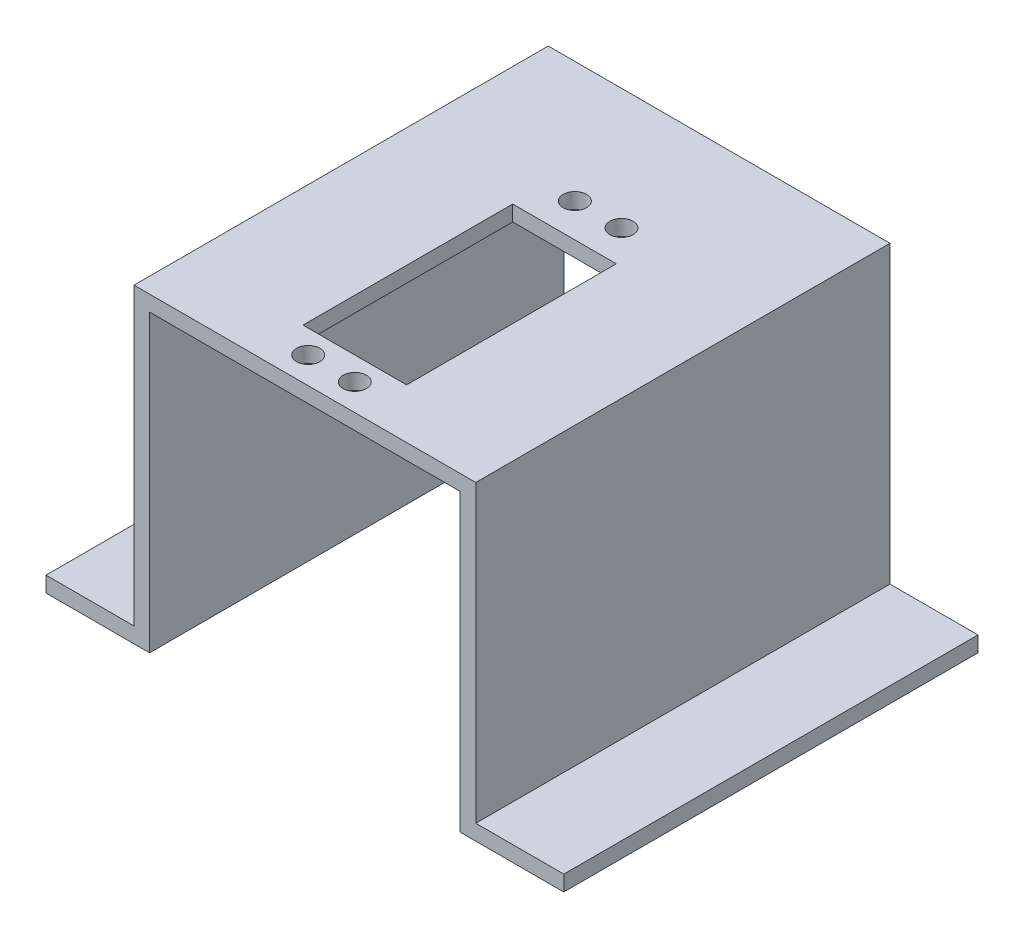
SolidWorks part; units mm, degrees
ref_plane "Front Plane" through (0, 0, 0) normal (0, 0, 1) x (1, 0, 0)
ref_plane "Top Plane" through (0, 0, 0) normal (0, 1, 0) x (1, 0, 0)
ref_plane "Right Plane" through (0, 0, 0) normal (1, 0, 0) x (0, 0, -1)
sketch "Sketch1" plane through (0, 0, 0) normal (0, 1, 0) x (1, 0, 0)
  line L1 (-50, 40) -> (50, 40)
  line L2 (-50, 40) -> (-50, -40)
  line L3 (-50, -40) -> (50, -40)
  line L4 (50, 40) -> (50, -40)
  line L5 (-50, 40) -> (50, -40) construction
  line L6 (-50, -40) -> (50, 40) construction
  point P0 (0, 0)
extrude "Boss-Extrude1" add sketch "Sketch1" along normal blind 60
sketch "Sketch2" plane through (0, 0, 40) normal (0, 0, 1) x (1, 0, 0)
  line L0 (-50, 0) -> (-30, 0) construction
  line L1 (-50, 0) -> (50, 0) construction
  line L2 (50, 0) -> (30, 0) construction
  line L3 (30, 0) -> (30, 60) construction
  line L4 (-50, 60) -> (50, 60) construction
  line L5 (30, 60) -> (-30, 60) construction
  line L6 (-30, 60) -> (-30, 0) construction
  line L7 (-30, 60) -> (-30, 5) construction
  line L8 (-30, 60) -> (-30, 57) construction
  line L9 (-30, 57) -> (30, 57) construction
  line L10 (30, 60) -> (33, 60) construction
  line L11 (33, 60) -> (33, 0) construction
  line L12 (33, 0) -> (50, 0) construction
  line L13 (50, 0) -> (50, 3) construction
  line L14 (50, 60) -> (50, 0) construction
  line L15 (50, 3) -> (33, 3) construction
  line L16 (-50, 0) -> (-50, 3) construction
  line L17 (-50, 60) -> (-50, 0) construction
  line L18 (-50, 3) -> (-30, 3) construction
  line L19 (-30, 3) -> (-30, 60) construction
  line L20 (-30, 0) -> (-33, 0) construction
  line L21 (-33, 0) -> (-33, 60) construction
  line L22 (-33, 60) -> (-30, 60) construction
  line L23 (-50, 3) -> (-33, 3)
  line L24 (-50, 3) -> (-50, 60)
  line L25 (-33, 3) -> (-33, 60)
  line L26 (-50, 60) -> (-33, 60)
  line L27 (-50, 3) -> (-33, 60) construction
  line L28 (-33, 3) -> (-50, 60) construction
  line L29 (-30, 57) -> (30, 57)
  line L30 (-30, 57) -> (-30, 0)
  line L31 (30, 57) -> (30, 0)
  line L32 (-30, 0) -> (30, 0)
  line L33 (-30, 57) -> (30, 0) construction
  line L34 (30, 57) -> (-30, 0) construction
  line L35 (33, 60) -> (33, 3)
  line L36 (33, 60) -> (50, 60)
  line L37 (33, 3) -> (50, 3)
  line L38 (50, 60) -> (50, 3)
  line L39 (33, 60) -> (50, 3) construction
  line L40 (33, 3) -> (50, 60) construction
  point P32 (-41.5, 31.5)
  point P33 (0, 28.5)
  point P35 (41.5, 31.5)
  dimension "D1" = 3
  dimension "D2" = 3
  dimension "D3" = 3
  dimension "D4" = 3
  dimension "D5" = 3
extrude "Cut-Extrude1" cut sketch "Sketch2" against normal blind 80
sketch "Sketch3" plane through (0, 60, 0) normal (0, 1, 0) x (1, 0, 0)
  line L0 (33, 40) -> (-33, -40) construction
  line L1 (-33, -40) -> (33, -40) construction
  line L2 (33, -40) -> (-33, 40) construction
  line L3 (-10, 0) -> (-10, 10.14) construction
  line L4 (-10, 10.14) -> (10, 10.14) construction
  line L5 (10, 10.14) -> (10, -30.36) construction
  line L6 (10, -30.36) -> (-10, -30.36) construction
  line L7 (-10, -30.36) -> (-10, 0) construction
  line L8 (-10, 10.14) -> (10, 10.14)
  line L9 (-10, 10.14) -> (-10, -30.36)
  line L10 (10, 10.14) -> (10, -30.36)
  line L11 (-10, -30.36) -> (10, -30.36)
  line L12 (-10, 10.14) -> (10, -30.36) construction
  line L13 (10, 10.14) -> (-10, -30.36) construction
  circle A0 centre (0, 0) radius 10 construction
  point P17 (0, -10.11)
extrude "Cut-Extrude2" cut sketch "Sketch3" against normal blind 3
sketch "Sketch4" plane through (0, 60, 0) normal (0, 1, 0) x (1, 0, 0)
  line L0 (10, -30.36) -> (9, -30.36) construction
  line L1 (-10, -30.36) -> (10, -30.36) construction
  line L2 (9, -30.36) -> (9, -37.36) construction
  line L3 (9, -37.36) -> (0, -37.36) construction
  line L4 (0, -37.36) -> (0, -30.36) construction
  line L5 (0, -30.36) -> (0, -34.86) construction
  line L6 (0, -34.86) -> (9, -34.86) construction
  line L7 (0, -37.36) -> (-9, -37.36) construction
  line L8 (-9, -37.36) -> (-9, -30.36) construction
  line L9 (0, -34.86) -> (-9, -34.86) construction
  line L10 (9, -30.36) -> (-9, -30.36) construction
  line L11 (9, -30.36) -> (9, 19.14) construction
  line L12 (-9, -30.36) -> (-9, 19.14) construction
  line L13 (9, 19.14) -> (-9, 19.14) construction
  line L14 (9, -30.36) -> (-9, 19.14) construction
  line L15 (-9, -30.36) -> (9, 19.14) construction
  line L16 (-9, 19.14) -> (-9, 16.64) construction
  line L17 (0, 19.14) -> (0, 10.14) construction
  line L18 (10, 10.14) -> (-10, 10.14) construction
  line L19 (-9, 16.64) -> (0, 16.64) construction
  line L20 (0, 16.64) -> (9, 16.64) construction
  circle A0 centre (4.5, -34.86) radius 2.25
  circle A1 centre (-4.5, -34.86) radius 2.25
  circle A2 centre (-4.5, 16.64) radius 2.25
  circle A3 centre (4.5, 16.64) radius 2.25
  point P21 (0, -5.61)
  dimension "D4" = 2.5
  dimension "D1" = 7
  dimension "D2" = 9
  dimension "D3" = 4.5
extrude "Cut-Extrude3" cut sketch "Sketch4" against normal blind 3
